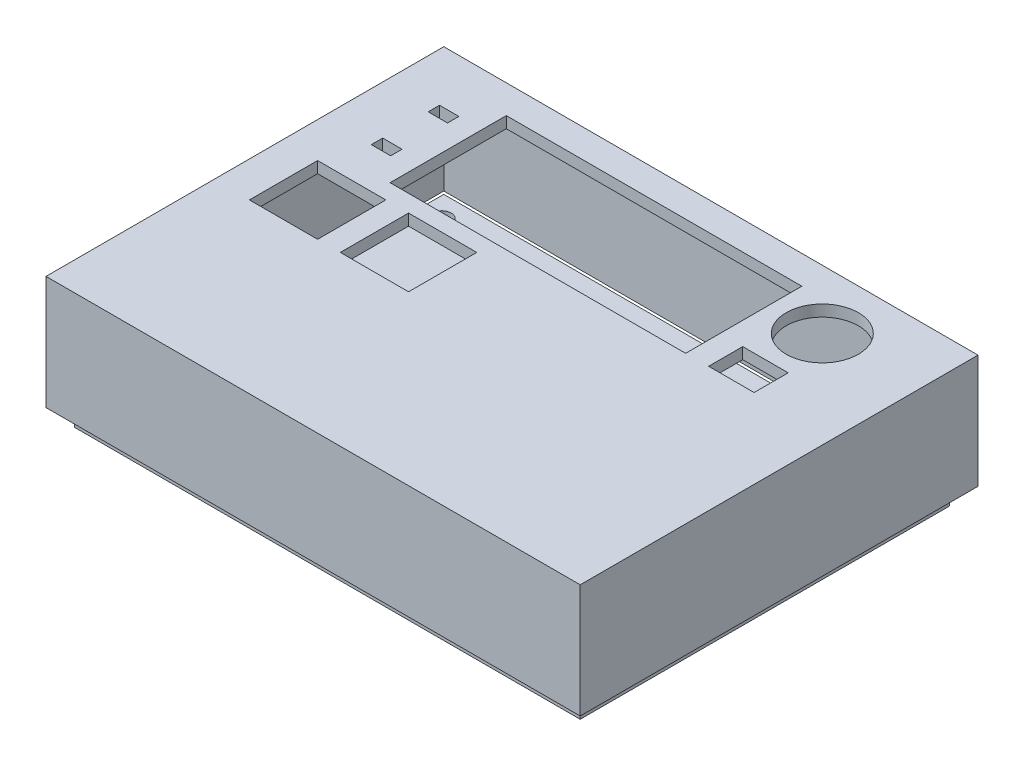
SolidWorks part; units mm, degrees
ref_plane "Front Plane" through (0, 0, 0) normal (0, 0, 1) x (1, 0, 0)
ref_plane "Top Plane" through (0, 0, 0) normal (0, 1, 0) x (1, 0, 0)
ref_plane "Right Plane" through (0, 0, 0) normal (1, 0, 0) x (0, 0, -1)
sketch "Sketch1" plane through (0, 0, 0) normal (0, 1, 0) x (1, 0, 0)
  line L0 (26.25, 25.8869) -> (18.25, 25.8869)
  line L7 (-53.75, -24.7156) -> (40.25, -24.7156)
  line L8 (-53.75, -24.7156) -> (-53.75, 45.2844)
  line L9 (-53.75, 45.2844) -> (40.25, 45.2844)
  line L10 (40.25, -24.7156) -> (40.25, 45.2844)
  line L11 (-41.8, 23.9844) -> (-45.2, 23.9844)
  line L15 (-37.75, 40.2844) -> (14.25, 40.2844)
  line L16 (-37.75, 40.2844) -> (-37.75, 19.8328)
  line L17 (-37.75, 19.8328) -> (14.25, 19.8328)
  line L18 (14.25, 40.2844) -> (14.25, 19.8328)
  line L21 (18.25, 19.8869) -> (26.25, 19.8869)
  line L22 (26.25, 25.8869) -> (26.25, 19.8869)
  line L27 (18.25, 25.8869) -> (18.25, 19.8869)
  line L28 (-47.5027, 16.8328) -> (-35.5027, 16.8328)
  line L29 (-47.5027, 16.8328) -> (-47.5027, 4.8328)
  line L30 (-47.5027, 4.8328) -> (-35.5027, 4.8328)
  line L31 (-35.5027, 16.8328) -> (-35.5027, 4.8328)
  line L33 (-31.5027, 16.8328) -> (-31.5027, 4.8328)
  line L34 (-19.5027, 4.8328) -> (-31.5027, 4.8328)
  line L35 (-19.5027, 16.8328) -> (-19.5027, 4.8328)
  line L36 (-19.5027, 16.8328) -> (-31.5027, 16.8328)
  line L41 (-41.8, 33.9844) -> (-45.2, 33.9844)
  line L42 (-41.8, 33.9844) -> (-41.8, 35.9844)
  line L43 (-41.8, 35.9844) -> (-45.2, 35.9844)
  line L44 (-45.2, 33.9844) -> (-45.2, 35.9844)
  line L45 (-41.8, 23.9844) -> (-41.8, 25.9844)
  line L46 (-41.8, 25.9844) -> (-45.2, 25.9844)
  line L47 (-45.2, 23.9844) -> (-45.2, 25.9844)
  circle A0 centre (23.25, 34.8869) radius 6.35
  point P0 (0, 0)
  point P6 (-6.75, 10.2844)
  dimension "D7" = 4
  dimension "D2" = 94
  dimension "D9" = 9
  dimension "D3" = 47
  dimension "D4" = 52
  dimension "D5" = 16
  dimension "D6" = 5
  dimension "D8" = 26
  dimension "D10" = 9
  dimension "D11" = 3
  dimension "D12" = 4
  dimension "D13" = 4.3
  dimension "D15" = 4.05
  dimension "D16" = 2
  dimension "D17" = 3.4
  dimension "D18" = 4.05
  dimension "D19" = 3.4
  dimension "D20" = 12
  dimension "D21" = 2
extrude "Boss-Extrude1" add sketch "Sketch1" along normal blind 2
sketch "Sketch2" plane through (0, 0, 0) normal (0, 1, 0) x (1, 0, 0)
  line L0 (-51.75, -22.7156) -> (38.25, -22.7156)
  line L1 (-53.75, 45.2844) -> (40.25, 45.2844)
  line L2 (-53.75, 45.2844) -> (-53.75, -24.7156)
  line L3 (-53.75, -24.7156) -> (40.25, -24.7156)
  line L4 (40.25, 45.2844) -> (40.25, -24.7156)
  line L9 (38.25, 43.2844) -> (38.25, -22.7156)
  line L13 (-51.75, -22.7156) -> (-51.75, 43.2844)
  line L14 (38.25, 43.2844) -> (-51.75, 43.2844)
  line L15 (31.6771, 43.2268) -> (-51.75, -22.7156) construction
  point P6 (-10, 10.2844)
  dimension "D1" = 66
  dimension "D2" = 2
  dimension "D3" = 2
  dimension "D4" = 2
extrude "Boss-Extrude2" add sketch "Sketch2" along normal blind 1 and the other way blind 18
sketch "Sketch3" plane through (40.25, 0, 0) normal (1, 0, 0) x (0, 0, -1)
  line L0 (-7.0156, -6.7933) -> (-14.0156, -6.7933)
  line L1 (-7.0156, -6.7933) -> (-7.0156, -1)
  line L2 (-7.0156, -1) -> (-14.0156, -1)
  line L3 (-14.0156, -6.7933) -> (-14.0156, -1)
extrude "Cut-Extrude1" cut sketch "Sketch3" against normal blind 10 and the other way blind 10 from surface starting at face at (-53.75, -8, -10.2844)
sketch "Sketch4" plane through (0, -18, 0) normal (0, -1, 0) x (1, 0, 0)
  line L0 (37.75, -42.7844) -> (37.75, 22.2156)
  line L5 (37.75, 22.2156) -> (-51.25, 22.2156)
  line L6 (-51.25, 22.2156) -> (-51.25, -42.7844)
  line L7 (-51.25, -42.7844) -> (37.75, -42.7844)
  line L14 (-42.1444, 8.2156) -> (-49.1444, 8.2156)
  line L15 (-42.1444, 8.2156) -> (-42.1444, 20.2156)
  line L16 (-42.1444, 20.2156) -> (-49.1444, 20.2156)
  line L17 (-49.1444, 8.2156) -> (-49.1444, 20.2156)
  line L18 (8.3556, 11.2156) -> (1.8556, 11.2156)
  line L19 (8.3556, 11.2156) -> (8.3556, 21.2156)
  line L20 (8.3556, 21.2156) -> (1.8556, 21.2156)
  line L21 (1.8556, 11.2156) -> (1.8556, 21.2156)
  dimension "D1" = 2.1056
  dimension "D2" = 12
  dimension "D3" = 2
  dimension "D4" = 7
  dimension "D5" = 44
  dimension "D6" = 1
  dimension "D7" = 10
  dimension "D8" = 6.5
extrude "Boss-Extrude3" add sketch "Sketch4" along normal blind 3 separate body
sketch "Sketch5" plane through (0, -21, 0) normal (0, -1, 0) x (-1, 0, 0)
  line L0 (51.25, 42.7844) -> (-37.75, 42.7844) construction
  line L1 (-37.75, 42.7844) -> (-37.75, -22.2156) construction
  line L2 (51.25, -22.2156) -> (51.25, 42.7844) construction
  line L3 (-37.75, -22.2156) -> (51.25, -22.2156) construction
  circle A3 centre (-34.75, 39.7844) radius 1.7
  circle A4 centre (35.25, -15.1156) radius 1.7
  circle A5 centre (47.75, 38.8844) radius 1.7
  point P12 (27.0514, -2.0782)
  point P15 (47.75, 37.1844)
  point P19 (36.1918, -16.5309)
  point P21 (-33.05, 39.7844)
  dimension "D1" = 3
  dimension "D3" = 3.9
  dimension "D5" = 16
  dimension "D2" = 3
  dimension "D4" = 3.5
  dimension "D6" = 7.1
extrude "Cut-Extrude5" cut sketch "Sketch5" against normal blind 3
